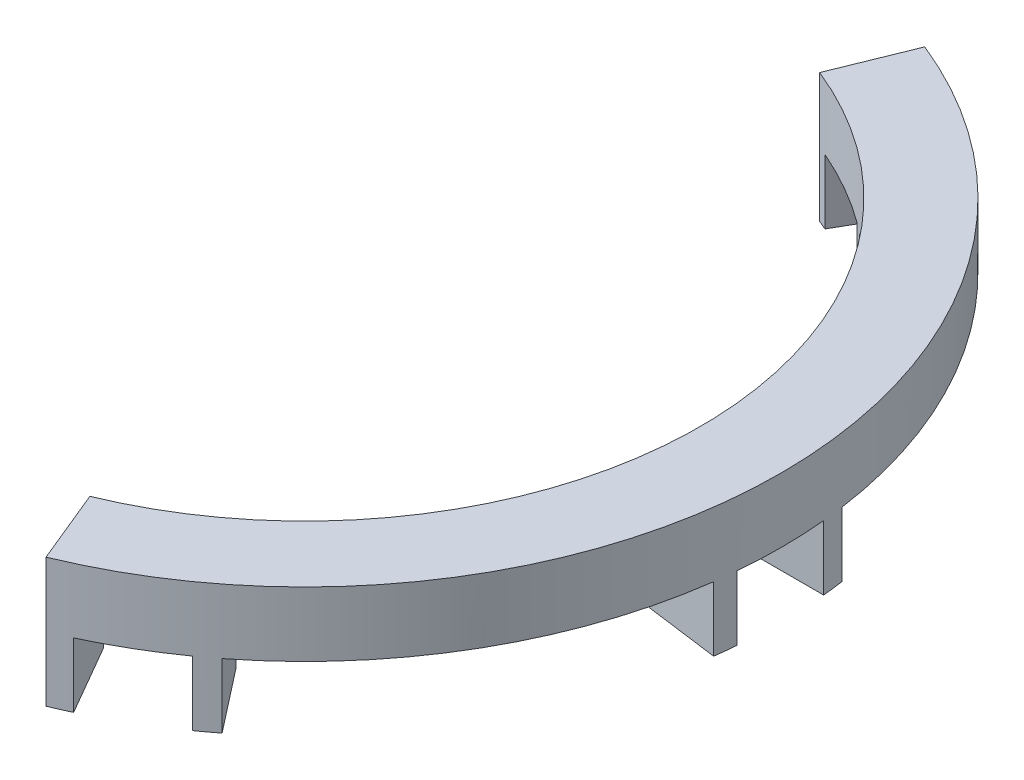
SolidWorks part; units mm, degrees
ref_plane "Front Plane" through (0, 0, 0) normal (0, 0, 1) x (1, 0, 0)
ref_plane "Top Plane" through (0, 0, 0) normal (0, 1, 0) x (1, 0, 0)
ref_plane "Right Plane" through (0, 0, 0) normal (1, 0, 0) x (0, 0, -1)
sketch "Sketch1" plane through (0, 0, 0) normal (0, 1, 0) x (1, 0, 0)
  line L2 (48.5304, 6.7678) -> (58.4345, 8.149)
  line L3 (18.4041, 45.4124) -> (22.1601, 54.6803)
  line L5 (29.9044, 38.8166) -> (36.0074, 46.7383)
  line L6 (48.5683, -6.4897) -> (58.4802, -7.8142)
  line L7 (58.7366, 5.569) -> (48.6825, 5.569)
  line L8 (58.7676, -5.231) -> (48.72, -5.231)
  line L9 (24.5454, 53.6519) -> (19.5184, 44.9448)
  line L10 (33.914, 48.2788) -> (28.8902, 39.5772)
  line L12 (30.1263, -38.6446) -> (36.2745, -46.5313)
  line L13 (18.6639, -45.3063) -> (22.4729, -54.5525)
  line L14 (34.1911, -48.0829) -> (29.1641, -39.3758)
  line L15 (24.8536, -53.5098) -> (19.8298, -44.8083)
  line L32 (-18.4041, -45.4124) -> (-22.1601, -54.6803) [skipped]
  line L33 (-29.9044, -38.8166) -> (-36.0074, -46.7383) [skipped]
  line L34 (-24.5454, -53.6519) -> (-19.5184, -44.9448) [skipped]
  line L35 (-33.914, -48.2788) -> (-28.8902, -39.5772) [skipped]
  line L37 (-48.5304, -6.7678) -> (-58.4345, -8.149) [skipped]
  line L38 (-48.5683, 6.4897) -> (-58.4802, 7.8142) [skipped]
  line L39 (-58.7366, -5.569) -> (-48.6825, -5.569) [skipped]
  line L40 (-58.7676, 5.231) -> (-48.72, 5.231) [skipped]
  line L42 (-30.1263, 38.6446) -> (-36.2745, 46.5313) [skipped]
  line L43 (-18.6639, 45.3063) -> (-22.4729, 54.5525) [skipped]
  line L44 (-34.1911, 48.0829) -> (-29.1641, 39.3758) [skipped]
  line L45 (-24.8536, 53.5098) -> (-19.8298, 44.8083) [skipped]
  arc A0 (22.4729, -54.5525) -> (24.8536, -53.5098) centre (0, 0) ccw
  arc A1 (18.6639, -45.3063) -> (19.8298, -44.8083) centre (0, 0) ccw
  arc A2 (36.0074, 46.7383) -> (33.914, 48.2788) centre (0, 0) ccw
  arc A3 (29.9044, 38.8166) -> (28.8902, 39.5772) centre (0, 0) ccw
  arc A4 (58.4802, -7.8142) -> (58.7676, -5.231) centre (0, 0) ccw
  arc A5 (48.5683, -6.4897) -> (48.72, -5.231) centre (0, 0) ccw
  arc A6 (24.5454, 53.6519) -> (22.1601, 54.6803) centre (0, 0) ccw
  arc A7 (19.5184, 44.9448) -> (18.4041, 45.4124) centre (0, 0) ccw
  arc A8 (58.7366, 5.569) -> (58.4345, 8.149) centre (0, 0) ccw
  arc A9 (48.6825, 5.569) -> (48.5304, 6.7678) centre (0, 0) ccw
  arc A10 (29.1641, -39.3758) -> (30.1263, -38.6446) centre (0, 0) ccw
  arc A11 (34.1911, -48.0829) -> (36.2745, -46.5313) centre (0, 0) ccw
  dimension "D1" = 118
  dimension "D10" = 98
  dimension "D5" = 6
extrude "Boss-Extrude1" add sketch "Sketch1" along normal blind 8
sketch "Sketch2" plane through (0, 8, 0) normal (0, 1, 0) x (1, 0, 0)
  line L0 (22.1601, 54.6803) -> (18.4041, 45.4124)
  line L1 (18.6639, -45.3063) -> (22.4729, -54.5525)
  arc A0 (22.4729, -54.5525) -> (22.1601, 54.6803) centre (0, 0) ccw
  arc A1 (18.6639, -45.3063) -> (18.4041, 45.4124) centre (0, 0) ccw
extrude "Boss-Extrude2" add sketch "Sketch2" along normal blind 8
